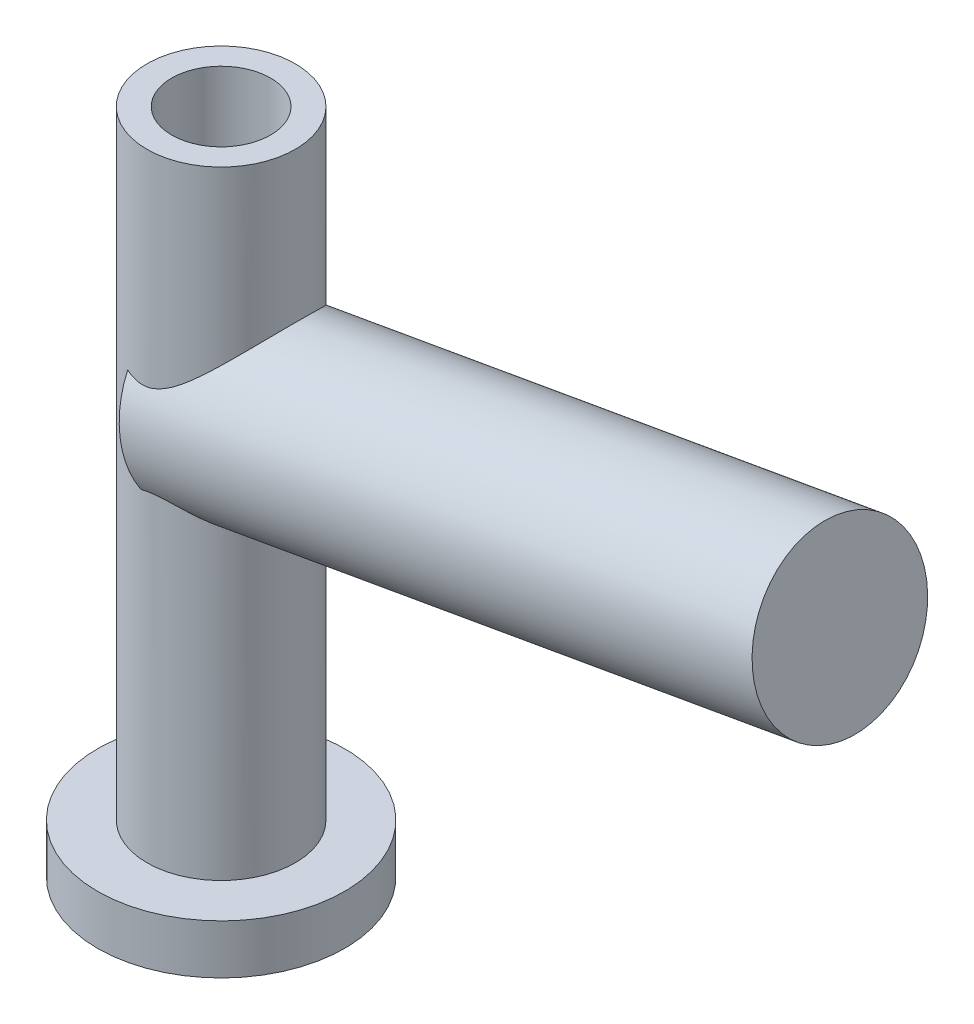
SolidWorks part; units mm, degrees
ref_plane "Front Plane" through (0, 0, 0) normal (0, 0, 1) x (1, 0, 0)
ref_plane "Top Plane" through (0, 0, 0) normal (0, 1, 0) x (1, 0, 0)
ref_plane "Right Plane" through (0, 0, 0) normal (1, 0, 0) x (0, 0, -1)
sketch "Sketch1" plane through (0, 0, 0) normal (0, 0, 1) x (1, 0, 0)
  line L0 (0, 135) -> (0, -135)
  line L1 (0, -135) -> (50, -135)
  line L2 (50, -135) -> (50, -115)
  line L3 (50, -115) -> (30, -115)
  line L4 (30, -115) -> (30, 135)
  line L5 (30, 135) -> (0, 135)
  dimension "D1" = 30
  dimension "D2" = 270
  dimension "D3" = 50
  dimension "D4" = 20
revolve "Revolve2" add sketch "Sketch1" angle 360 about L0
ref_axis "Axis2" through (0, 0, -55) along (0, 0, 1)
ref_plane "Plane2" through (0, 0, 0) normal (0.9848, 0.1736, 0) x (0, 0, 1)
sketch "Sketch3" plane through (0, 0, 0) normal (0.9848, 0.1736, 0) x (0, 0, 1)
  circle A0 centre (0, -32.949) radius 35
  ellipse E0 centre (0, -132.949) end of major axis (-30, -132.949) minor radius 5.2094 construction
  dimension "D1" = 70
  dimension "D2" = 100
extrude "Boss-Extrude1" add sketch "Sketch3" along normal blind 260
sketch "Sketch4" plane through (0, 135, 0) normal (0, 1, 0) x (1, 0, 0)
  circle A0 centre (0, 0) radius 20
  dimension "D1" = 40
extrude "Cut-Extrude1" cut sketch "Sketch4" against normal through all
